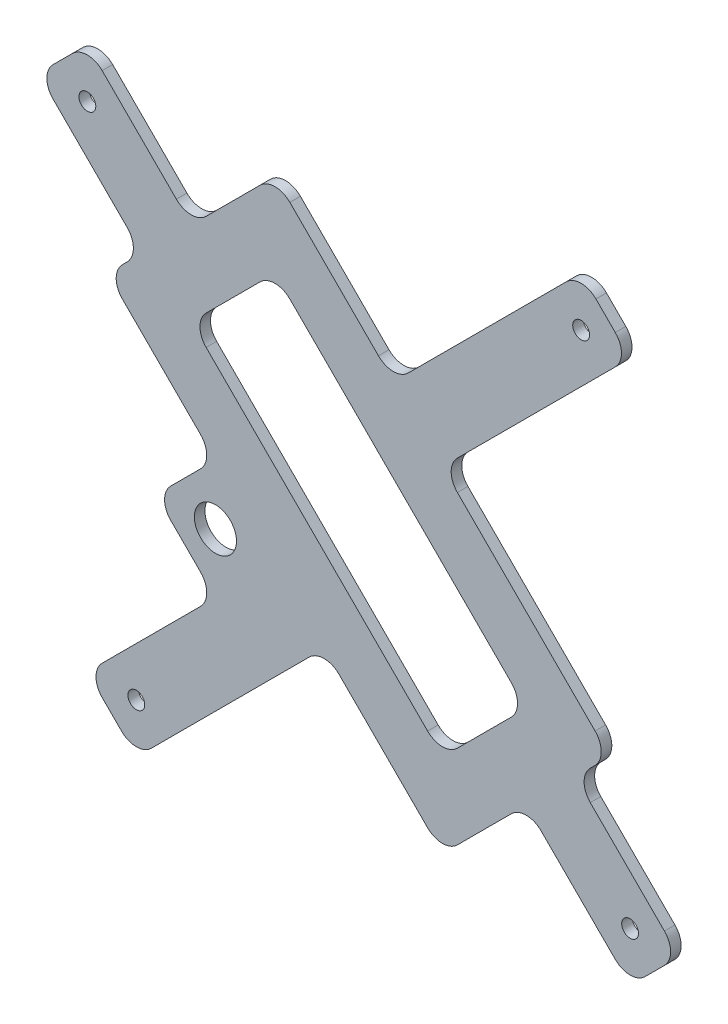
SolidWorks part; units mm, degrees
ref_plane "Front Plane" through (0, 0, 0) normal (0, 0, 1) x (1, 0, 0)
ref_plane "Top Plane" through (0, 0, 0) normal (0, 1, 0) x (1, 0, 0)
ref_plane "Right Plane" through (0, 0, 0) normal (1, 0, 0) x (0, 0, -1)
sketch "Sketch2" plane through (0, 0, 70.5078) normal (0, 0, -1) x (-1, 0, 0)
  line L0 (-93.5818, -113.4839) -> (-76.7527, -96.6548)
  line L1 (-99.2387, -113.4839) -> (-109.4917, -103.2309)
  line L2 (-125.4016, -81.6641) -> (-99.2387, -55.5012)
  line L3 (-35.5991, -49.8443) -> (-36.5183, -48.9251)
  line L4 (-99.2387, -49.8443) -> (-129.2412, -19.8419)
  line L5 (-129.2412, -14.185) -> (-125.5642, -10.508)
  line L6 (-119.9074, -10.508) -> (-89.9049, -40.5105)
  line L7 (-45.8521, -33.9344) -> (-31.7595, -19.8419)
  line L8 (-26.1027, -19.8419) -> (-22.4257, -23.5188)
  line L9 (-22.4257, -29.1757) -> (-36.5183, -43.2682)
  line L10 (-50.4483, -98.6347) -> (-31.7595, -117.3235)
  line L11 (-31.7595, -122.9803) -> (-35.4365, -126.6573)
  line L12 (-41.0934, -126.6573) -> (-71.0958, -96.6548)
  line L13 (-115.1486, -103.2309) -> (-129.2412, -117.3235)
  line L14 (-134.898, -117.3235) -> (-138.575, -113.6465)
  line L15 (-138.575, -107.9897) -> (-124.4824, -93.8971)
  line L16 (-124.4824, -88.2402) -> (-125.4016, -87.321)
  line L17 (-51.509, -33.9344) -> (-61.762, -23.6814)
  line L18 (-84.248, -40.5105) -> (-67.4189, -23.6814)
  line L19 (-50.4483, -70.3504) -> (-35.5991, -55.5012)
  line L20 (-109.4917, -81.6641) -> (-67.4189, -39.5913)
  line L21 (-61.762, -39.5913) -> (-51.509, -49.8443)
  line L22 (-51.509, -55.5012) -> (-93.5818, -97.574)
  line L23 (-99.2387, -97.574) -> (-109.4917, -87.321)
  line L24 (-50.4483, -76.0073) -> (-44.7915, -81.6641)
  line L25 (-44.7915, -87.321) -> (-50.4483, -92.9778)
  line L26 (-53.2767, -73.1789) -> (-53.2767, -95.8063) construction
  circle A0 centre (-132.055, -110.8327) radius 1.6
  circle A1 centre (-28.9457, -26.3327) radius 1.6
  circle A2 centre (-122.7504, -17.028) radius 1.6
  circle A3 centre (-38.2504, -120.1373) radius 1.6
  arc A4 (-67.4189, -39.5913) -> (-61.762, -39.5913) centre (-64.5905, -42.4197) cw
  arc A5 (-51.509, -49.8443) -> (-51.509, -55.5012) centre (-54.3374, -52.6728) cw
  arc A6 (-93.5818, -97.574) -> (-99.2387, -97.574) centre (-96.4103, -94.7456) cw
  arc A7 (-109.4917, -81.6641) -> (-109.4917, -87.321) centre (-106.6633, -84.4926) ccw
  arc A8 (-125.5642, -10.508) -> (-119.9074, -10.508) centre (-122.7358, -13.3365) cw
  arc A9 (-129.2412, -19.8419) -> (-129.2412, -14.185) centre (-126.4127, -17.0134) cw
  arc A10 (-99.2387, -49.8443) -> (-99.2387, -55.5012) centre (-102.0671, -52.6728) cw
  arc A11 (-89.9049, -40.5105) -> (-84.248, -40.5105) centre (-87.0765, -37.6821) ccw
  arc A12 (-67.4189, -23.6814) -> (-61.762, -23.6814) centre (-64.5905, -26.5098) cw
  arc A13 (-51.509, -33.9344) -> (-45.8521, -33.9344) centre (-48.6806, -31.106) ccw
  arc A14 (-31.7595, -19.8419) -> (-26.1027, -19.8419) centre (-28.9311, -22.6703) cw
  arc A15 (-22.4257, -23.5188) -> (-22.4257, -29.1757) centre (-25.2542, -26.3472) cw
  arc A16 (-36.5183, -48.9251) -> (-36.5183, -43.2682) centre (-33.6899, -46.0967) cw
  arc A17 (-125.4016, -87.321) -> (-125.4016, -81.6641) centre (-122.5732, -84.4926) cw
  arc A18 (-124.4824, -93.8971) -> (-124.4824, -88.2402) centre (-127.3108, -91.0687) ccw
  arc A19 (-115.1486, -103.2309) -> (-109.4917, -103.2309) centre (-112.3202, -106.0593) cw
  arc A20 (-35.5991, -55.5012) -> (-35.5991, -49.8443) centre (-38.4275, -52.6728) ccw
  arc A22 (-71.0958, -96.6548) -> (-76.7527, -96.6548) centre (-73.9243, -99.4832) ccw
  arc A23 (-31.7595, -117.3235) -> (-31.7595, -122.9803) centre (-34.588, -120.1519) cw
  arc A24 (-35.4365, -126.6573) -> (-41.0934, -126.6573) centre (-38.2649, -123.8289) cw
  arc A25 (-93.5818, -113.4839) -> (-99.2387, -113.4839) centre (-96.4103, -110.6555) cw
  arc A26 (-129.2412, -117.3235) -> (-134.898, -117.3235) centre (-132.0696, -114.495) cw
  arc A27 (-138.575, -113.6465) -> (-138.575, -107.9897) centre (-135.7466, -110.8181) cw
  circle A28 centre (-53.2767, -84.4926) radius 4
  arc A29 (-50.4483, -98.6347) -> (-50.4483, -92.9778) centre (-47.6199, -95.8063) cw
  arc A30 (-50.4483, -76.0073) -> (-50.4483, -70.3504) centre (-47.6199, -73.1789) cw
  arc A31 (-44.7915, -81.6641) -> (-44.7915, -87.321) centre (-47.6199, -84.4926) cw
  point P6 (-122.7504, -17.028)
  point P8 (-80.5004, -68.5827)
  point P25 (-80.5004, -68.5827)
  dimension "D6" = 4
  dimension "D9" = 4
  dimension "D1" = 45
  dimension "D2" = 90
  dimension "D3" = 22.5
  dimension "D4" = 13.2
  dimension "D5" = 6.6
  dimension "D7" = 16
  dimension "D8" = 16
extrude "Boss-Extrude1" add sketch "Sketch2" along normal blind 2
ref_axis "Axis1" through (132.055, -110.8327, 70.5078) along (0, 0, -1)
ref_axis "Axis2" through (28.9457, -26.3327, 70.5078) along (0, 0, -1)
